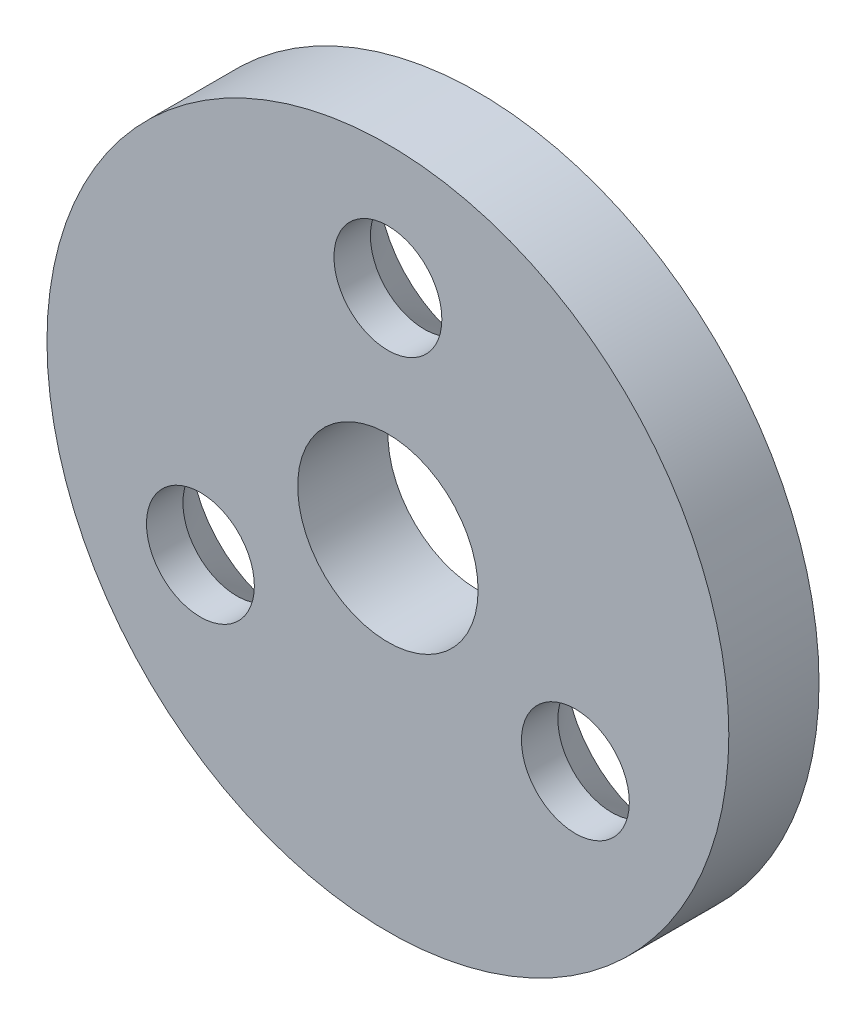
SolidWorks part; units mm, degrees
material "Delrin 2700 NC010, Low Viscosity Acetal Copolymer (SS)"
ref_plane "Front" through (0, 0, 0) normal (0, 0, 1) x (1, 0, 0)
ref_plane "Top" through (0, 0, 0) normal (0, 1, 0) x (1, 0, 0)
ref_plane "Right" through (0, 0, 0) normal (1, 0, 0) x (0, 0, -1)
ref_axis "side-side" through (80.9, 0, 0) along (-1, 0, 0)
ref_axis "up-down" through (0, 50, 0) along (0, -1, 0)
ref_axis "front-back" through (0, 0, -80.9) along (0, 0, 1)
sketch "Sketch1" plane through (0, 0, 0) normal (0, 0, 1) x (1, 0, 0)
  circle A0 centre (0, 0) radius 3.175
  circle A1 centre (0, 0) radius 12
  dimension "D1" = 6.35
  dimension "D2" = 24
extrude "Boss-Extrude1" add sketch "Sketch1" along normal blind 3.175
hole_wizard "CSK for #6 Flat Head Machine Screw1" positions "Sketch2" profile "Sketch3" countersink size "#6" standard "ANSI Inch"
sketch "Sketch2" plane through (0, 0, 0) normal (0, 0, -1) x (-1, 0, 0)
  line L3 (0, 7.62) -> (0, 0) construction
  line L4 (0, 0) -> (-6.5991, -3.81) construction
  line L6 (0, 0) -> (6.5991, -3.81) construction
  point P0 (0, 7.62)
  point P2 (-6.5991, -3.81)
  point P5 (6.5991, -3.81)
  point P38 (0, 0)
  point P39 (5.7162, -3.1597)
  point P40 (0, 0)
  point P41 (5.6587, -4.9693)
  dimension "D1" = 120
  dimension "D2" = 7.62
sketch "Sketch3" plane through (0, 7.62, 0) normal (1, 0, 0) x (0, 1, 0)
  line L0 (0, 0) -> (0, 12.1138)
  line L1 (0, 12.1138) -> (1.8986, 10.973)
  line L2 (1.8986, 10.973) -> (1.8986, 1.892)
  line L3 (1.8986, 1.892) -> (3.5433, 0)
  line L5 (3.5433, 0) -> (0, 0)
  line L6 (-1.8986, 1.892) -> (-3.5433, 0) construction
  line L10 (0, 12.1138) -> (-1.8987, 10.973) construction
  line L11 (0, -6.35) -> (0, 107.95) construction
  dimension "Hole Dia." = 3.7973
  dimension "Hole Depth" = 10.973
  dimension "Near C'Sink Dia." = 7.0866
  dimension "Near C'Sink Angle" = 82
  dimension "Drill Angle" = 118
